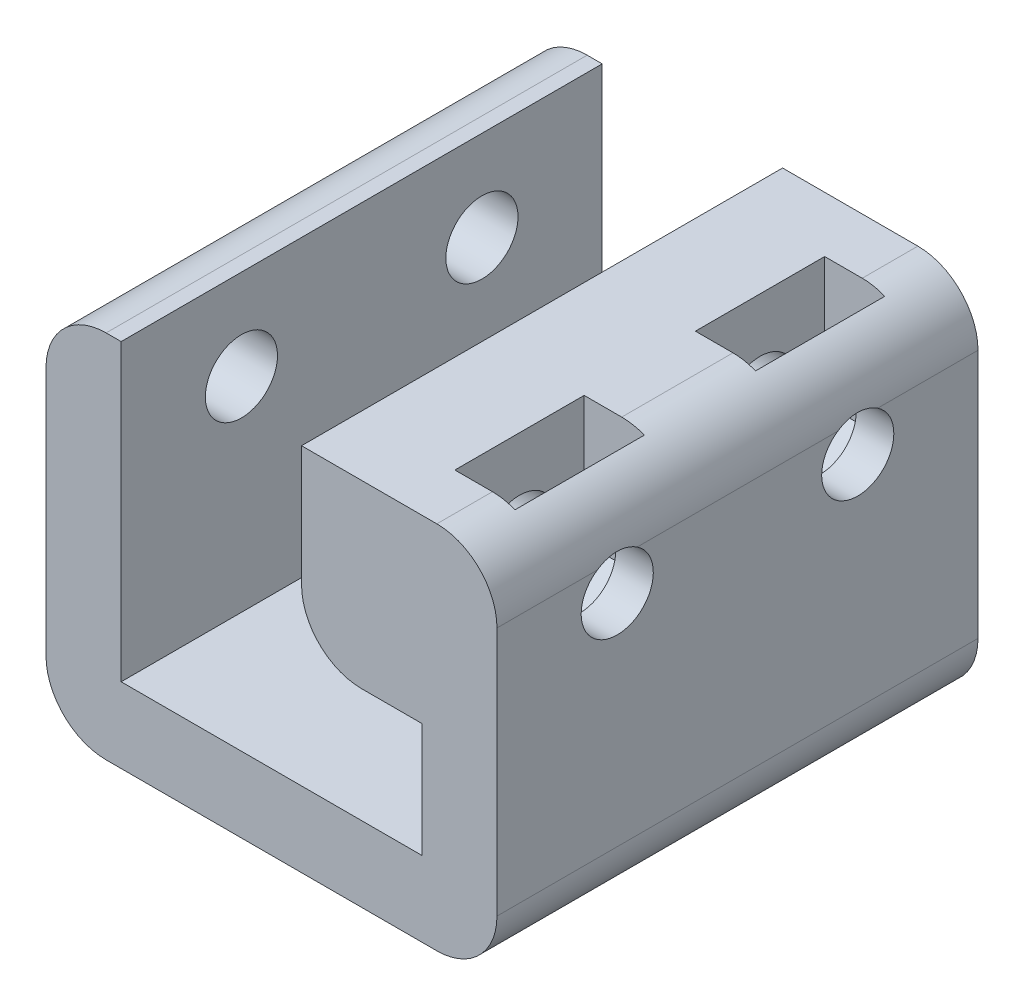
SolidWorks part; units mm, degrees
ref_plane "Front Plane" through (0, 0, 0) normal (0, 0, 1) x (1, 0, 0)
ref_plane "Top Plane" through (0, 0, 0) normal (0, 1, 0) x (1, 0, 0)
ref_plane "Right Plane" through (0, 0, 0) normal (1, 0, 0) x (0, 0, -1)
sketch "Sketch3" plane through (0, 0, 0) normal (0, 1, 0) x (1, 0, 0)
  line L1 (-7.5, -8) -> (7.5, -8)
  line L2 (-7.5, -8) -> (-7.5, 8)
  line L3 (-7.5, 8) -> (7.5, 8)
  line L4 (7.5, -8) -> (7.5, 8)
  line L5 (-7.5, -8) -> (7.5, 8) construction
  line L6 (-7.5, 8) -> (7.5, -8) construction
  point P0 (0, 0)
  dimension "D1" = 16
  dimension "D2" = 15
extrude "Boss-Extrude1" add sketch "Sketch3" along normal blind 2.5
sketch "Sketch4" plane through (0, 2.5, 0) normal (0, 1, 0) x (1, 0, 0)
  line L0 (-7.5, -8) -> (7.5, -8) construction
  line L1 (-7.5, 8) -> (-5, 8)
  line L2 (-7.5, 8) -> (-7.5, -8)
  line L3 (-7.5, -8) -> (-5, -8)
  line L4 (-5, 8) -> (-5, -8)
  line L5 (7.5, 8) -> (-7.5, 8) construction
  line L6 (7.5, -8) -> (5, -8)
  line L7 (7.5, -8) -> (7.5, 8)
  line L8 (7.5, 8) -> (5, 8)
  line L9 (5, -8) -> (5, 8)
  dimension "D1" = 2.5
  dimension "D2" = 2.5
extrude "Boss-Extrude2" add sketch "Sketch4" along normal blind 9.8
sketch "Sketch5" plane through (7.5, 0, 0) normal (1, 0, 0) x (0, 0, -1)
  line L0 (8, 12.3) -> (8, 0) construction
  line L1 (-8, 12.3) -> (8, 12.3) construction
  line L2 (-8, 12.3) -> (-8, 6.3) construction
  line L3 (-8, 6.3) -> (8, 6.3) construction
  line L4 (8, 12.3) -> (8, 6.3) construction
  line L5 (-8, 9.3) -> (8, 9.3) construction
  line L6 (0, 6.3) -> (0, 12.3) construction
  circle A0 centre (-4, 9.3) radius 1.5888
  circle A1 centre (4, 9.3) radius 1.6103
  dimension "D1" = 6
  dimension "D3" = 4
hole_wizard "M2 Clearance Hole1" positions "Sketch6" profile "Sketch8" hole size "M2" standard "AS"
sketch "Sketch6" plane through (7.5, 0, 0) normal (1, 0, 0) x (0, 0, -1)
  point P0 (-4, 9.3)
  point P3 (4, 9.3)
sketch "Sketch8" plane through (7.5, 9.3, 4) normal (0, 1, 0) x (0, 0, -1)
  line L0 (0, 0) -> (0, 15.721)
  line L1 (0, 15.721) -> (1.2, 15)
  line L2 (1.2, 15) -> (1.2, 0)
  line L5 (1.2, 0) -> (0, 0)
  line L10 (0, 15.721) -> (-1.2, 15) construction
  line L11 (0, -6.35) -> (0, 107.95) construction
  dimension "Hole Dia." = 2.4
  dimension "Hole Depth" = 15
  dimension "Drill Angle" = 118
fillet "Fillet1" radius 2 2 edges at (7.5, 0, 0) (-7.5, 0, 0)
sketch "Sketch9" plane through (5, 0, 0) normal (-1, 0, 0) x (0, 0, 1)
  line L0 (8, 12.3) -> (8, 2.5) construction
  line L1 (-8, 12.3) -> (8, 12.3)
  line L2 (-8, 12.3) -> (-8, 6.3)
  line L3 (-8, 6.3) -> (8, 6.3)
  line L4 (8, 12.3) -> (8, 6.3)
  circle A0 centre (-4, 9.3) radius 1.2
  circle A1 centre (4, 9.3) radius 1.2
  circle A2 centre (4, 9.3) radius 1.2 construction
  circle A3 centre (-4, 9.3) radius 1.2 construction
  dimension "D1" = 6
extrude "Boss-Extrude3" add sketch "Sketch9" along normal blind 4
fillet "Fillet2" radius 2 3 edges at (-7.5, 12.3, 0) (7.5, 12.3, 0) (1, 6.3, 0)
ref_plane "Plane1" through (6.25, 0, 0) normal (1, 0, 0) x (0, 0, -1)
sketch "Sketch10" plane through (7.5, 0, 0) normal (1, 0, 0) x (0, 0, -1)
  line L0 (-8, 10.3) -> (-8, 2) construction
  line L1 (-4, 6.8174) -> (-1.85, 8.0587)
  line L2 (-1.85, 8.0587) -> (-1.85, 10.5413)
  line L3 (-2.925, 11.162) -> (-4, 11.7826) construction
  line L4 (-5.075, 11.162) -> (-6.15, 10.5413) construction
  line L5 (-6.15, 10.5413) -> (-6.15, 8.0587)
  line L6 (-6.15, 8.0587) -> (-4, 6.8174)
  line L7 (4, 6.8174) -> (6.15, 8.0587)
  line L8 (6.15, 8.0587) -> (6.15, 10.5413)
  line L9 (6.15, 10.5413) -> (5.075, 11.162) construction
  line L10 (2.925, 11.162) -> (1.85, 10.5413) construction
  line L11 (1.85, 10.5413) -> (1.85, 8.0587)
  line L12 (1.85, 8.0587) -> (4, 6.8174)
  line L13 (8, 10.3) -> (8, 2) construction
  line L14 (-6.15, 10.5413) -> (-6.15, 12.3)
  line L15 (-8, 12.3) -> (8, 12.3) construction
  line L16 (-1.85, 10.5413) -> (-1.85, 12.3)
  line L17 (-1.85, 12.3) -> (-6.15, 12.3)
  line L18 (1.85, 10.5413) -> (1.85, 12.3)
  line L19 (1.85, 12.3) -> (6.15, 12.3)
  line L20 (6.15, 12.3) -> (6.15, 10.5413)
  line L21 (4, 11.7826) -> (2.925, 11.162) construction
  line L22 (5.075, 11.162) -> (4, 11.7826) construction
  line L23 (-1.85, 10.5413) -> (-2.925, 11.162) construction
  line L24 (-4, 11.7826) -> (-5.075, 11.162) construction
  arc A0 (-6.15, 9.3) -> (-1.85, 9.3) centre (-4, 9.3) ccw construction
  arc A1 (1.85, 9.3) -> (6.15, 9.3) centre (4, 9.3) ccw construction
  arc A2 (5.075, 11.162) -> (2.925, 11.162) centre (4, 9.3) ccw construction
  arc A3 (6.15, 9.3) -> (5.075, 11.162) centre (4, 9.3) ccw construction
  arc A4 (2.925, 11.162) -> (1.85, 9.3) centre (4, 9.3) ccw construction
  arc A5 (-1.85, 9.3) -> (-2.925, 11.162) centre (-4, 9.3) ccw construction
  arc A6 (-2.925, 11.162) -> (-5.075, 11.162) centre (-4, 9.3) ccw construction
  arc A7 (-5.075, 11.162) -> (-6.15, 9.3) centre (-4, 9.3) ccw construction
  point P10 (-1.85, 9.3)
  dimension "D1" = 4.3
  dimension "D2" = 4.3
extrude "Cut-Extrude1" cut sketch "Sketch10" against normal blind 2 from surface starting at plane "Plane1"
equation "\"D2@Sketch4\"=\"D1@Sketch4\""
equation "\"D3@Sketch5\"=\"D2@Sketch5\""
equation "\"D2@Sketch10\"=\"D1@Sketch10\""
